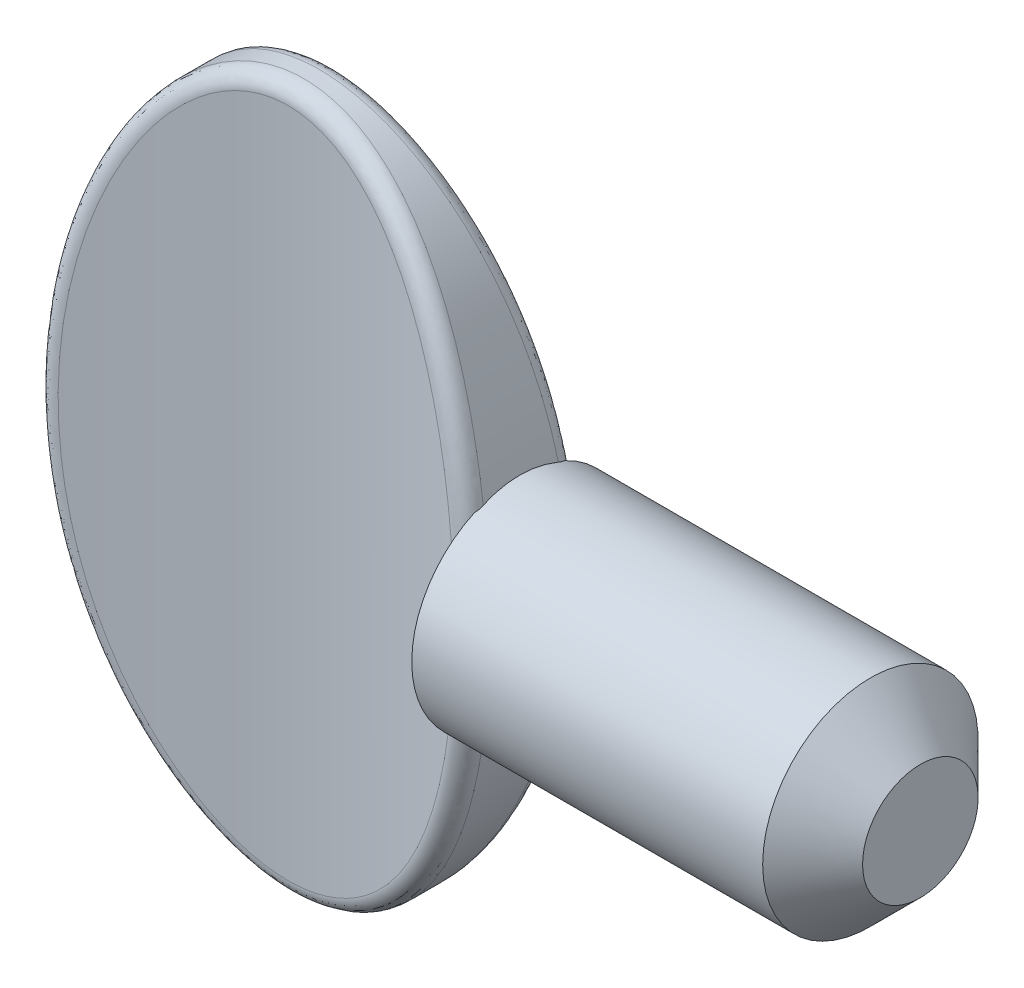
SolidWorks part; units mm, degrees
ref_plane "Front" through (0, 0, 0) normal (0, 0, 1) x (1, 0, 0)
ref_plane "Top" through (0, 0, 0) normal (0, 1, 0) x (1, 0, 0)
ref_plane "Right" through (0, 0, 0) normal (1, 0, 0) x (0, 0, -1)
ref_axis "Axis1" through (-50, 0, 0) along (1, 0, 0)
sketch "Sketch1" plane through (0, 0, 0) normal (0, 0, 1) x (1, 0, 0)
  line L0 (0, 0) -> (9.906, 0) construction
  line L1 (4.7413, -1.7526) -> (4.7413, 1.7526)
  line L2 (4.7413, -1.7526) -> (3.3847, -1.7526) construction
  ellipse E0 centre (0, 0) end of major axis (0, -5.715) minor radius 3.556
  dimension "D2" = 1.1853
  dimension "B" = 7.112
  dimension "L" = 6.35
extrude "Extrude1" add sketch "Sketch1" along normal mid plane 2.032
sketch "Sketch2" plane through (0, 0, 0) normal (0, 1, 0) x (1, 0, 0)
  line L0 (3.556, 1.016) -> (-3.556, 1.016) construction
  line L1 (0, 0) -> (0, 1.1721) construction
  line L2 (-1.7991, 0) -> (2.0444, 0) construction
  line L3 (-3.556, -1.016) -> (3.556, -1.016) construction
  line L6 (-3.556, 1.016) -> (-3.556, -1.016)
  line L7 (3.556, 1.016) -> (3.556, -1.016)
  arc A0 (-3.556, 1.016) -> (3.556, 1.016) centre (0, 10.6553) ccw
  arc A1 (-3.556, -1.016) -> (3.556, -1.016) centre (0, -10.6553) cw
extrude "Cut-Extrude1" cut sketch "Sketch2" against normal through all and the other way through all flip side to cut
fillet "Fillet3" radius 0.254 2 edges at (-3.4679, -1.2641, 0.984) (0.2073, 5.7053, -0.3831)
sketch "Sketch3" plane through (0, 0, 0) normal (0, 1, 0) x (1, 0, 0)
  line L0 (9.906, 0) -> (9.906, 0.9398)
  line L1 (0, 0) -> (21.0288, 0) construction
  line L2 (0, 0) -> (9.906, 0) construction
  line L3 (4.7413, 1.7526) -> (4.7413, 0) construction
  line L4 (4.7413, 1.7526) -> (9.0932, 1.7526)
  line L5 (9.906, 0.9398) -> (9.0932, 1.7526)
  line L6 (4.7413, 1.7526) -> (3.3847, 1.7526)
  line L7 (2.5775, 0.7096) -> (2.5775, 0)
  line L8 (3.3847, 0) -> (3.3847, 1.7526) construction
  line L9 (2.5775, 0) -> (9.906, 0)
  arc A0 (3.3847, 1.7526) -> (2.5775, 0.7096) centre (2.3072, 1.7526) cw
  arc A3 (-3.556, 1.016) -> (3.556, 1.016) centre (0, 10.6553) ccw construction
  dimension "D1" = 45
revolve "Revolve1" add sketch "Sketch3" angle 360 about L0
cosmetic thread "Cosmetic Thread1" [suppressed]
sketch "Sketch4" plane through (0, 0, 0) normal (0, 0, 1) x (1, 0, 0)
  line L0 (0, 0) -> (27.7993, 0) construction
  line L1 (8.8879, 1.7526) -> (9.0932, 1.397)
  line L2 (9.0932, 1.397) -> (9.2985, 1.7526)
  line L3 (9.2985, 1.7526) -> (9.2985, 2.1632)
  line L4 (9.2985, 2.1632) -> (8.8879, 2.1632)
  line L5 (8.8879, 2.1632) -> (8.8879, 1.7526)
  line L6 (9.0932, 1.7526) -> (9.0932, -1.7526) construction
  dimension "D1" = 2.794
  dimension "D2" = 3.5052
revolve "Cut-Revolve10" [suppressed] cut sketch "Sketch4" angle 360 about L0
pattern_linear "LPattern10" [suppressed] count 11 along (-1, 0, 0) of bodies 109
equation "\"D2@Sketch1\" = \"B@Sketch1\" / 6"
equation "\"D1@Fillet3\" = \"C1@Sketch2\" / 3"
equation "\"DIA@Sketch3\" = \"D@Sketch1\""
equation "\"D1@Cosmetic Thread1\" = \"L@Sketch1\" -  ( \"D@Sketch1\" - \"flat_dia@Sketch3\" )  / 2"
equation "\"D1@Sketch4\" = \"D2@Cosmetic Thread1\""
equation "\"D2@Sketch4\" = \"DIA@Sketch3\""
equation "\"D1@LPattern10\" = \"D1@Cosmetic Thread1\" / \"P@LPattern10\" "
